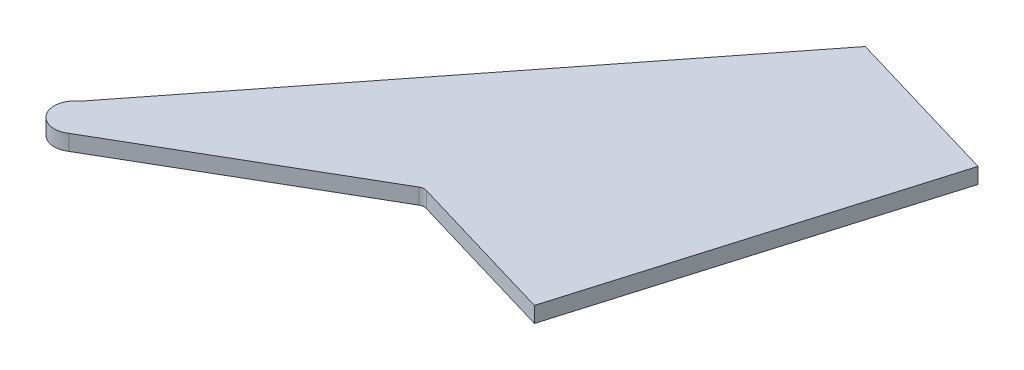
SolidWorks part; units mm, degrees
material "6061 Alloy"
ref_plane "Front Plane" through (0, 0, 0) normal (0, 0, 1) x (1, 0, 0)
ref_plane "Top Plane" through (0, 0, 0) normal (0, 1, 0) x (1, 0, 0)
ref_plane "Right Plane" through (0, 0, 0) normal (1, 0, 0) x (0, 0, -1)
sketch "Sketch1" plane through (0, 0, 0) normal (0, 1, 0) x (1, 0, 0)
  line L0 (53.8544, 73.3734) -> (102.5625, 58.9454)
  line L1 (22.9946, -31.525) -> (-44.3261, -70.5626)
  line L2 (-51.2626, -60.5757) -> (53.8544, 73.3734)
  line L4 (102.5625, 58.9454) -> (71.7331, -45.1328)
  line L5 (71.7331, -45.1328) -> (24.9902, -31.2869)
  arc A0 (-44.3261, -70.5626) -> (-51.2626, -60.5757) centre (-47.7944, -65.5691) cw
  arc A2 (22.9946, -31.525) -> (24.9902, -31.2869) centre (24.2688, -33.7223) cw
  dimension "D1" = 2.54
extrude "Boss-Extrude1" add sketch "Sketch1" along normal blind 4.7625
